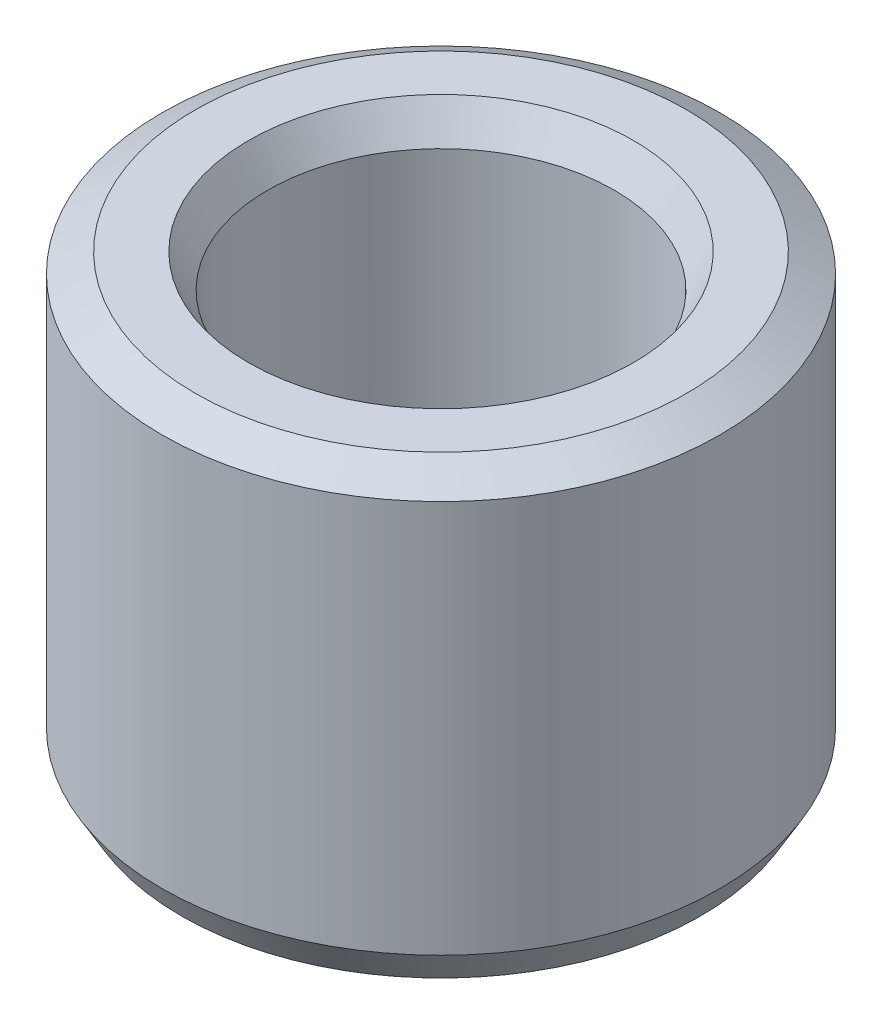
SolidWorks part; units mm, degrees
ref_plane "Front Plane" through (0, 0, 0) normal (0, 0, 1) x (1, 0, 0)
ref_plane "Top Plane" through (0, 0, 0) normal (0, 1, 0) x (1, 0, 0)
ref_plane "Right Plane" through (0, 0, 0) normal (1, 0, 0) x (0, 0, -1)
sketch "Sketch1" plane through (0, 0, 0) normal (0, 1, 0) x (1, 0, 0)
  circle A0 centre (0, 0) radius 25
  dimension "SLEEVE_OD" = 50
extrude "Boss-Extrude1" add sketch "Sketch1" along normal blind 39.9165
sketch "Sketch2" plane through (0, 0, 0) normal (0, 1, 0) x (1, 0, 0)
  circle A0 centre (0, 0) radius 15.521
  dimension "BORE_D" = 31.042
extrude "Cut-Extrude1" cut sketch "Sketch2" along normal through all
chamfer "Chamfer1" distance 1.7254 angle 60 4 edges at (0, 39.9165, 15.521) (0, 0, 15.521) (0, 0, 25) (0, 39.9165, 25) first distance on face at (0, 39.9165, 15.521) first distance on face at (0, 0, 15.521) first distance on face at (0, 39.9165, 25)
